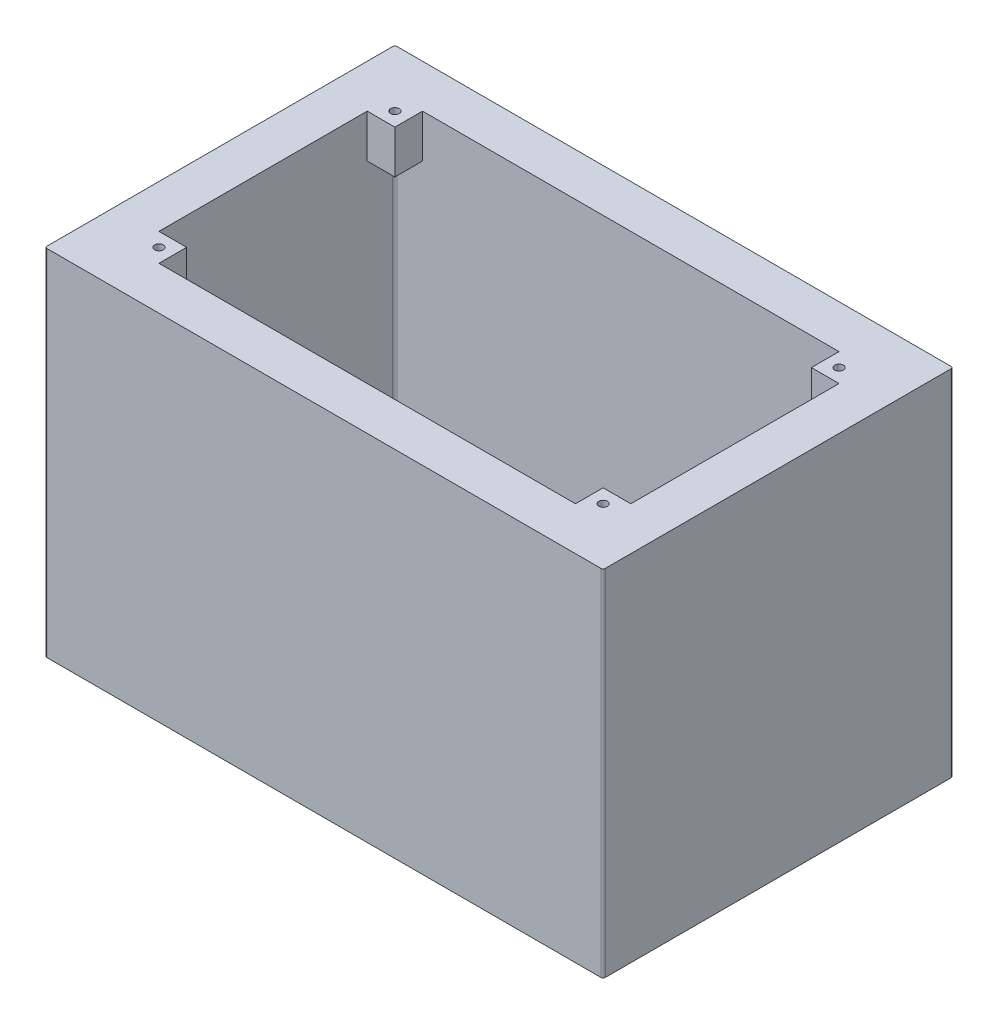
SolidWorks part; units mm, degrees
ref_plane "Front Plane" through (0, 0, 0) normal (0, 0, 1) x (1, 0, 0)
ref_plane "Top Plane" through (0, 0, 0) normal (0, 1, 0) x (1, 0, 0)
ref_plane "Right Plane" through (0, 0, 0) normal (1, 0, 0) x (0, 0, -1)
sketch "Sketch1" plane through (0, 0, 0) normal (0, 1, 0) x (1, 0, 0)
  line L1 (-32.3, -20.25) -> (32.3, -20.25)
  line L2 (-32.3, -20.25) -> (-32.3, 20.25)
  line L3 (-32.3, 20.25) -> (32.3, 20.25)
  line L4 (32.3, -20.25) -> (32.3, 20.25)
  line L5 (-32.3, -20.25) -> (32.3, 20.25) construction
  line L6 (-32.3, 20.25) -> (32.3, -20.25) construction
  point P0 (0, 0)
  dimension "D1" = 64.6
  dimension "D2" = 40.5
extrude "Boss-Extrude1" add sketch "Sketch1" along normal blind 2.5 contours L2 L1 L4 L3
sketch "Sketch3" plane through (0, 2.5, 0) normal (0, 1, 0) x (1, 0, 0)
  line L0 (-27.3, 15.25) -> (-27.3, -15.25)
  line L1 (-32.3, 20.25) -> (32.3, 20.25)
  line L2 (-32.3, 20.25) -> (-32.3, -20.25)
  line L3 (-32.3, -20.25) -> (32.3, -20.25)
  line L4 (32.3, 20.25) -> (32.3, -20.25)
  line L5 (-27.3, -15.25) -> (27.3, -15.25)
  line L6 (27.3, 15.25) -> (27.3, -15.25)
  line L7 (-27.3, 15.25) -> (27.3, 15.25)
  dimension "D1" = 5
extrude "Boss-Extrude4" add sketch "Sketch3" along normal blind 38.5
sketch "Sketch4" plane through (0, 41, 0) normal (0, 1, 0) x (1, 0, 0)
  line L0 (0, 0) -> (0, 15.25) construction
  line L1 (-27.3, 15.25) -> (-24.1, 15.25)
  line L2 (-27.3, 15.25) -> (-27.3, 12.05)
  line L3 (-27.3, 12.05) -> (-24.1, 12.05)
  line L4 (-24.1, 15.25) -> (-24.1, 12.05)
  line L5 (27.3, 15.25) -> (-27.3, 15.25) construction
  line L6 (0, 15.25) -> (0, 25.0147) construction
  line L7 (0, 0) -> (27.3, 0) construction
  line L8 (27.3, -15.25) -> (27.3, 15.25) construction
  line L9 (27.3, 0) -> (36.4444, 0) construction
  line L10 (-25.7, 15.25) -> (-25.7, 12.05)
  line L11 (27.3, 12.05) -> (24.1, 12.05)
  line L12 (24.1, 15.25) -> (24.1, 12.05)
  line L13 (27.3, 15.25) -> (24.1, 15.25)
  line L14 (27.3, 15.25) -> (27.3, 12.05)
  line L15 (27.3, -15.25) -> (27.3, -12.05)
  line L16 (27.3, -15.25) -> (24.1, -15.25)
  line L17 (24.1, -15.25) -> (24.1, -12.05)
  line L18 (27.3, -12.05) -> (24.1, -12.05)
  line L19 (-27.3, -15.25) -> (-24.1, -15.25)
  line L20 (-24.1, -15.25) -> (-24.1, -12.05)
  line L21 (-27.3, -12.05) -> (-24.1, -12.05)
  line L22 (-27.3, -15.25) -> (-27.3, -12.05)
  circle A0 centre (-25.7, 13.65) radius 0.5
  circle A1 centre (25.7, 13.65) radius 0.5
  circle A2 centre (25.7, -13.65) radius 0.5
  circle A3 centre (-25.7, -13.65) radius 0.5
  dimension "D3" = 1
  dimension "D1" = 3.2
  dimension "D2" = 3.2
extrude "Boss-Extrude7" add sketch "Sketch4" against normal blind 5 contours A0 L10 A2 A1 L3 | A0 L10 L3 L4 L1 | A2 L12 L11 A3 A1 | A3 L18 L17 A2 | L21 A1 L20 A3 region at (-26.5488, 41, -13.65) region at (-24.8512, 41, -13.65) region at (25.7, 41, -12.0953) region at (25.7, 41, 15.2047) region at (-27.2547, 41, 13.65)
fillet "Fillet1" radius 0.25 4 edges at (32.3, 20.5, -20.25) (32.3, 20.5, 20.25) (-32.3, 20.5, -20.25) (-32.3, 20.5, 20.25)
fillet "Fillet2" radius 0.25 5 edges at (27.3, 19.25, 15.25) (-27.3, 19.25, 15.25) (27.3, 19.25, -15.25) (0, 2.5, -15.25) (-27.3, 19.25, -15.25)
sketch "Sketch6" plane through (-32.3, 0, 0) normal (-1, 0, 0) x (0, 0, 1)
  line L1 (20, 0) -> (8, 0)
  line L2 (20, 0) -> (20, 12) construction
  line L3 (20, 12) -> (8, 12) construction
  line L4 (8, 0) -> (8, 12) construction
  circle A0 centre (8, 12) radius 2
  dimension "D3" = 4
  dimension "D1" = 12
  dimension "D2" = 12
extrude "Cut-Extrude1" cut sketch "Sketch6" against normal blind 5 contours A0 region at (-32.3, 12, 8)
fillet "Fillet4" radius 0.3 1 edges at (-32.3, 12, 10)
